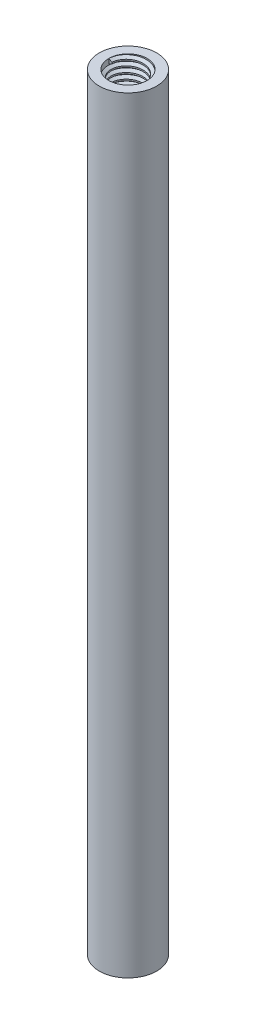
SolidWorks part; units mm, degrees
material "AISI 1020"
ref_plane "Front Plane" through (0, 0, 0) normal (0, 0, 1) x (1, 0, 0)
ref_plane "Top Plane" through (0, 0, 0) normal (0, 1, 0) x (1, 0, 0)
ref_plane "Right Plane" through (0, 0, 0) normal (1, 0, 0) x (0, 0, -1)
sketch "Sketch1" plane through (0, 0, 0) normal (0, 1, 0) x (1, 0, 0)
  circle A0 centre (0, 0) radius 7.5
  circle A1 centre (0, 0) radius 5
  dimension "D1" = 15
  dimension "D3" = 10
  dimension "D2" = 2.5
extrude "Boss-Extrude1" add sketch "Sketch1" along normal mid plane 200
thread "Thread1" pitch 1.5 method extrude profile "Thread Profile1" start angle 0, offset 0, length 15, pitch 1.5, diameter 10
ref_plane "Plane1" through (-5, 100, 0) normal (0, 0, 1) x (-1, 0, 0)
sketch "Thread Profile1" plane through (-5, 100, 0) normal (0, 0, 1) x (-1, 0, 0)
  line L0 (0, 0) -> (0, 1.5) construction
  line L11 (0, 0) -> (0, 1.3125)
  line L12 (0, 1.3125) -> (-0.8119, 0.8437)
  line L13 (-0.8119, 0.8437) -> (-0.8119, 0.4687)
  line L15 (-0.8119, 0.4687) -> (0, 0)
  line L17 (-0.8119, 0.6562) -> (0, 0.6562) construction
  point P2 (0, 0)
  dimension "Pitch" = 1.5
  dimension "Profile_Angle" = 60
  dimension "Profile_Land" = 0.375
  dimension "Profile_Height" = 0.8119
thread "Thread2" pitch 1.5 method extrude profile "Thread Profile2" start angle 0, offset 0, length 15, pitch 1.5, diameter 10
ref_plane "Plane2" through (5, -100, 0) normal (0, 0, 1) x (1, 0, 0)
sketch "Thread Profile2" plane through (5, -100, 0) normal (0, 0, 1) x (1, 0, 0)
  line L0 (0, 0) -> (0, 1.5) construction
  line L11 (0, 0) -> (0, 1.3125)
  line L12 (0, 1.3125) -> (-0.8119, 0.8437)
  line L13 (-0.8119, 0.8437) -> (-0.8119, 0.4687)
  line L15 (-0.8119, 0.4687) -> (0, 0)
  line L17 (-0.8119, 0.6562) -> (0, 0.6562) construction
  point P2 (0, 0)
  dimension "Pitch" = 1.5
  dimension "Profile_Angle" = 60
  dimension "Profile_Land" = 0.375
  dimension "Profile_Height" = 0.8119
equation "\"RodDIa\"= 15"
equation "\"D1@Sketch1\"=\"RodDIa\""
equation "\"RodTickness\"= 2.5"
equation "\"D2@Sketch1\"=\"RodTickness\""
equation "\"RodLength\"= 200"
equation "\"D1@Boss-Extrude1\"=\"RodLength\""
